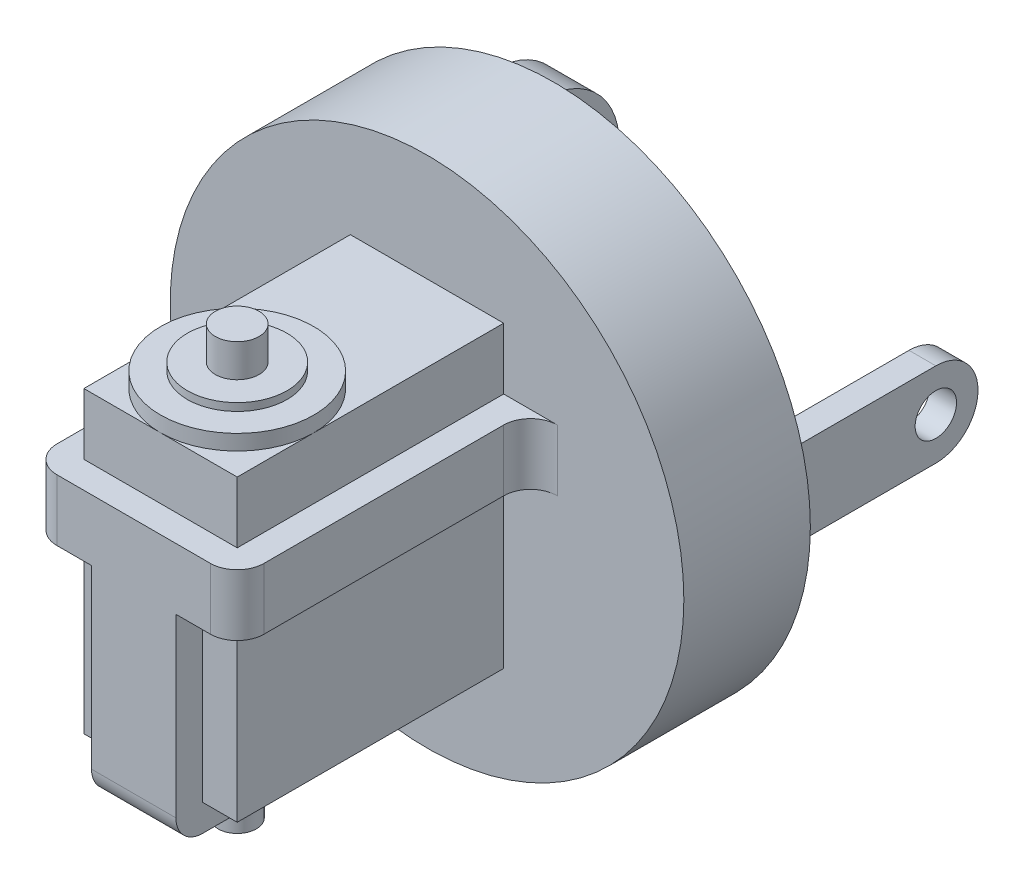
SolidWorks part; units mm, degrees
ref_plane "Front Plane" through (0, 0, 0) normal (0, 0, 1) x (1, 0, 0)
ref_plane "Top Plane" through (0, 0, 0) normal (0, 1, 0) x (1, 0, 0)
ref_plane "Right Plane" through (0, 0, 0) normal (1, 0, 0) x (0, 0, -1)
sketch "Sketch1" plane through (0, 0, 0) normal (0, 0, 1) x (1, 0, 0)
  circle A1 centre (0, 0) radius 33.5
extrude "Boss-Extrude3" add sketch "Sketch1" along normal blind 16.5 contours A1
sketch "Sketch2" plane through (0, 0, 16.5) normal (0, 0, 1) x (1, 0, 0)
  line L0 (0, 0) -> (33.5, 0) construction
  line L1 (-10, 19.5) -> (10, 19.5)
  line L2 (-10, 19.5) -> (-10, -19.5)
  line L3 (-10, -19.5) -> (10, -19.5)
  line L4 (10, 19.5) -> (10, -19.5)
  line L5 (0, 0) -> (0, -33.5) construction
  circle A0 centre (0, 0) radius 33.5 construction
  dimension "D1" = 10
  dimension "D2" = 19.5
extrude "Boss-Extrude4" add sketch "Sketch2" along normal blind 34.758
sketch "Sketch3" plane through (0, 19.5, 0) normal (0, 1, 0) x (1, 0, 0)
  circle A0 centre (0, -41.258) radius 10
  circle A1 centre (0, -41.258) radius 6.5
  circle A2 centre (0, -41.258) radius 2.85
extrude "Boss-Extrude5" add sketch "Sketch3" along normal blind 2 contours A0 A1 region at (-9.7172, 19.5, 41.258)
extrude "Boss-Extrude6" add sketch "Sketch3<3>" along normal blind 3 contours A1
sketch "Sketch3<3>" plane through (0, 19.5, 0) normal (0, 1, 0) x (1, 0, 0) same geometry as "Sketch3"
extrude "Boss-Extrude7" add sketch "Sketch3<4>" along normal blind 7.3 contours A2
sketch "Sketch3<4>" plane through (0, 19.5, 0) normal (0, 1, 0) x (1, 0, 0) same geometry as "Sketch3"
sketch "Sketch5" plane through (0, 0, 51.258) normal (0, 0, 1) x (1, 0, 0)
  line L0 (-10, -19.5) -> (10, -19.5) construction
  line L1 (-5.5, -23) -> (5.5, -23)
  line L2 (-5.5, -23) -> (-5.5, -19.5)
  line L3 (-5.5, -19.5) -> (5.5, -19.5)
  line L4 (5.5, -23) -> (5.5, -19.5)
  line L5 (10, -19.5) -> (10, 19.5) construction
  line L6 (10, 11.5) -> (13.5, 11.5)
  line L7 (10, 11.5) -> (10, 3.5)
  line L8 (10, 3.5) -> (13.5, 3.5)
  line L9 (13.5, 11.5) -> (13.5, 3.5)
  line L10 (-10, 19.5) -> (-10, -19.5) construction
  line L11 (-10, 11.5) -> (-13.5, 11.5)
  line L12 (-10, 11.5) -> (-10, 3.5)
  line L13 (-10, 3.5) -> (-13.5, 3.5)
  line L14 (-13.5, 11.5) -> (-13.5, 3.5)
  line L15 (-10, -19.5) -> (10, -19.5) construction
  point P19 (0, 0)
  point P20 (0, 0)
  point P21 (-11.75, 3.5)
  dimension "D1" = 5.5
  dimension "D2" = 23
  dimension "D3" = 23
  dimension "D4" = 8
  dimension "D5" = 8
  dimension "D6" = 3.5
  dimension "D7" = 3.5
extrude "Boss-Extrude8" add sketch "Sketch5" against normal up to surface (34.758 mm away) up to face at (0, 0, 16.5)
sketch "Sketch6" plane through (0, 0, 51.258) normal (0, 0, 1) x (1, 0, 0)
  line L1 (-13.5, 11.5) -> (13.5, 11.5)
  line L2 (-13.5, 11.5) -> (-13.5, 3.5)
  line L3 (-13.5, 3.5) -> (13.5, 3.5)
  line L4 (13.5, 11.5) -> (13.5, 3.5)
  line L5 (5.5, -23) -> (-5.5, -23)
  line L6 (5.5, -23) -> (5.5, 11.5)
  line L7 (5.5, 11.5) -> (-5.5, 11.5)
  line L8 (-5.5, -23) -> (-5.5, 11.5)
  point P11 (-5.5, -23)
  line M6 (-10, 11.5) -> (-13.5, 11.5)
  line M7 (-13.5, 11.5) -> (-13.5, 3.5)
  line M8 (-13.5, 3.5) -> (-10, 3.5)
  line M11 (-5.5, -19.5) -> (-5.5, -23)
  line M12 (-5.5, -23) -> (5.5, -23)
  line M13 (5.5, -23) -> (5.5, -19.5)
  line M16 (10, 3.5) -> (13.5, 3.5)
  line M17 (13.5, 3.5) -> (13.5, 11.5)
  line M18 (13.5, 11.5) -> (10, 11.5)
extrude "Boss-Extrude9" add sketch "Sketch6" along normal blind 3.5 contours L8 L3 L6 L1 | L6 L3 L1 M16 M17 M18 | L8 L6 L3 M11 M12 M13 | L3 L8 L1 M6 M7 M8 region at (-9.5, 7.5, 51.258) region at (0, 7.5, 51.258) region at (9.5, 7.5, 51.258) region at (0, -9.75, 51.258)
sketch "Sketch7" plane through (0, -23, 0) normal (0, -1, 0) x (1, 0, 0)
  circle A0 centre (0, 41.258) radius 2.5
extrude "Boss-Extrude10" add sketch "Sketch7" along normal blind 6 contours A0
fillet "Fillet1" radius 3.5 2 edges at (-13.5, 7.5, 54.758) (13.5, 7.5, 54.758)
fillet "Fillet2" radius 3.5 1 edges at (0, -23, 54.758)
fillet "Fillet3" radius 3.5 1 edges at (13.5, 7.5, 16.5)
fillet "Fillet4" radius 3.5 1 edges at (-13.5, 7.5, 16.5)
sketch "Sketch9" plane through (0, 0, 0) normal (0, 0, -1) x (-1, 0, 0)
  line L1 (-29, 5.5) -> (-25.5, 5.5)
  line L2 (-29, 5.5) -> (-29, -5.5)
  line L3 (-29, -5.5) -> (-25.5, -5.5)
  line L4 (-25.5, 5.5) -> (-25.5, -5.5)
  line L5 (25.3, 10) -> (28.8, 10)
  line L6 (25.3, 10) -> (25.3, -10)
  line L7 (25.3, -10) -> (28.8, -10)
  line L8 (28.8, 10) -> (28.8, -10)
  dimension "D1" = 3.5
  dimension "D2" = 3.5
  dimension "D3" = 11
  dimension "D4" = 20
  dimension "D5" = 10
  dimension "D6" = 5.5
  dimension "D7" = 25.5
  dimension "D8" = 25.3
extrude "Boss-Extrude11" add sketch "Sketch9" along normal blind 30.867 contours L8 L7 L6 L5
extrude "Boss-Extrude12" add sketch "Sketch9<3>" along normal blind 27 contours L4 L3 L2 L1
sketch "Sketch9<3>" plane through (0, 0, 0) normal (0, 0, -1) x (-1, 0, 0) same geometry as "Sketch9"
sketch "Sketch10" plane through (-25.3, 0, 0) normal (1, 0, 0) x (0, 0, -1)
  line L0 (20.867, 0) -> (20.867, -10) construction
  circle A0 centre (20.867, 0) radius 10
  circle A1 centre (20.867, 0) radius 5
  circle A2 centre (20.867, 0) radius 3
  circle A3 centre (20.867, -7) radius 1.5
  circle A4 centre (20.867, 0) radius 1.5
  point P8 (0, 0)
  line M2 (0, -10) -> (30.867, -10)
  line M3 (30.867, -10) -> (30.867, 10)
  line M4 (30.867, 10) -> (0, 10)
  dimension "D1" = 7
extrude "Cut-Extrude1" cut sketch "Sketch10" against normal through all contours A0 M3 M4 | A0 M2 M3 region at (-25.3, -7.7663, -28.6333) region at (-25.3, 7.7663, -28.6333)
extrude "Boss-Extrude13" add sketch "Sketch10<3>" along normal blind 3 contours A0
sketch "Sketch10<3>" plane through (-25.3, 0, 0) normal (1, 0, 0) x (0, 0, -1) same geometry as "Sketch10"
extrude "Boss-Extrude14" add sketch "Sketch10<4>" along normal blind 4.5 contours A2 | A1
sketch "Sketch10<4>" plane through (-25.3, 0, 0) normal (1, 0, 0) x (0, 0, -1) same geometry as "Sketch10"
extrude "Cut-Extrude4" cut sketch "Sketch10<7>" against normal blind 18.5 and the other way blind 16 contours A3
sketch "Sketch10<7>" plane through (-25.3, 0, 0) normal (1, 0, 0) x (0, 0, -1) same geometry as "Sketch10"
pattern_circular "CirPattern3" count 4 over 360 about axis through (-20.8, 0, -20.867) along (1, 0, 0) of "Cut-Extrude4"
sketch "Sketch11" plane through (-22.3, 0, 0) normal (1, 0, 0) x (0, 0, -1)
  circle A0 centre (20.867, 0) radius 1.5
extrude "Cut-Extrude6" cut sketch "Sketch11" against normal through all
sketch "Sketch13" plane through (29, 0, 0) normal (1, 0, 0) x (0, 0, -1)
  circle A0 centre (20.867, 0) radius 2.7
  circle A1 centre (20.867, 0) radius 5.5
  line M3 (0, -5.5) -> (27, -5.5)
  line M4 (27, -5.5) -> (27, 5.5)
  line M5 (27, 5.5) -> (0, 5.5)
extrude "Cut-Extrude10" cut sketch "Sketch13" against normal blind 15.5 contours A1 M3 M4 M5 | A0 region at (29, 0, -20.867) region at (29, 3.9781, -24.8451)
sketch "Sketch14" plane through (0, 0, 0) normal (0, 0, -1) x (-1, 0, 0)
  line L0 (0, 0) -> (0, 18) construction
  line L1 (0, 0) -> (9, 15.5885)
  line L2 (0, 0) -> (-9, 15.5885)
  circle A0 centre (0, 0) radius 1.25
  circle A1 centre (0, 0) radius 9
  circle A2 centre (0, 0) radius 18
  dimension "D1" = 60
  dimension "D2" = 30
extrude "Cut-Extrude11" cut sketch "Sketch14" against normal blind 3.5 contours L0 A1 L1 A2 | A1 L0 A2 L2 region at (3.5822, 13.369, 0) region at (-3.5822, 13.369, 0)
pattern_circular "CirPattern4" count 4 over 360 about axis through (0, 0, 0) along (0, 0, 1) of "Cut-Extrude11"
extrude "Cut-Extrude12" cut sketch "Sketch14<3>" against normal blind 3.5 contours A0
sketch "Sketch14<3>" plane through (0, 0, 0) normal (0, 0, -1) x (-1, 0, 0) same geometry as "Sketch14"
ref_plane "Plane2" through (33.5, 0, 0) normal (1, 0, 0) x (0, 0, -1)
ref_plane "Plane3" through (0, 0, 0) normal (1, 0, 0) x (0, 0, -1)
sketch "Sketch15" plane through (0, 0, 0) normal (1, 0, 0) x (0, 0, -1)
  line L0 (20.867, 0) -> (20.867, 1.5) construction
  line L1 (20.867, 0) -> (22.367, 0) construction
  circle A0 centre (20.867, 0) radius 1.5
